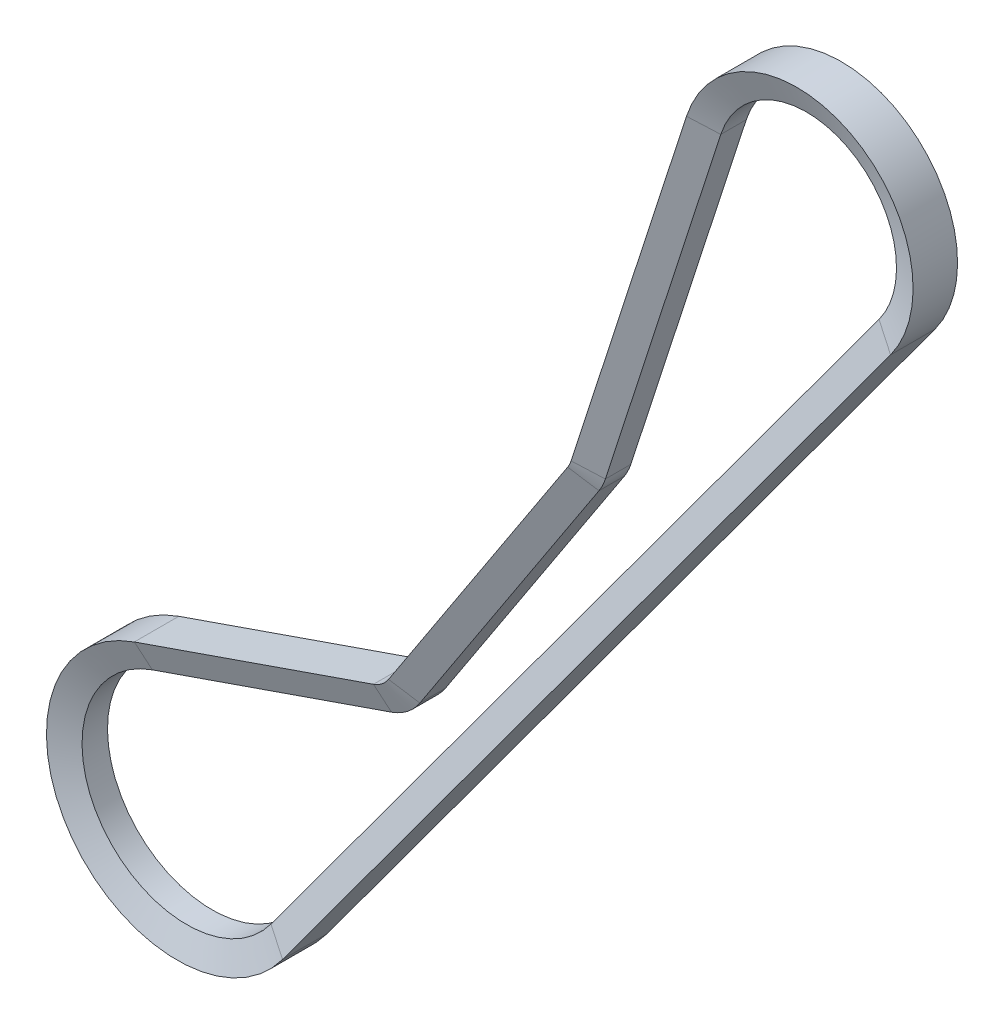
SolidWorks part; units mm, degrees
ref_plane "Front Plane" through (0, 0, 0) normal (0, 0, 1) x (1, 0, 0)
ref_plane "Top Plane" through (0, 0, 0) normal (0, 1, 0) x (1, 0, 0)
ref_plane "Right Plane" through (0, 0, 0) normal (1, 0, 0) x (0, 0, -1)
sketch "Sketch2" plane through (0, 0, 0) normal (0, 0, 1) x (1, 0, 0)
  line L0 (0, 0) -> (1, 0) construction
  line L1 (0, 0) -> (0, 1) construction
  line L12 (20.0468, -14.7273) -> (-110.1915, -192.0074)
  line L14 (-141.9298, -148.9752) -> (-90.7076, -131.214)
  line L15 (-87.4763, -128.6941) -> (-49.1172, -70.1401)
  line L16 (-48.3882, -68.6181) -> (-23.6632, 7.6693)
  arc A4 (-110.1915, -192.0074) -> (-141.9298, -148.9752) centre (-132.7567, -175.43) cw
  arc A7 (-23.6632, 7.6693) -> (20.0468, -14.7273) centre (0, 0) cw
  arc A8 (-90.7076, -131.214) -> (-87.4763, -128.6941) centre (-92.788, -125.2144) ccw
  arc A9 (-49.1172, -70.1401) -> (-48.3882, -68.6181) centre (-54.4289, -66.6603) ccw
ref_plane "Plane4" through (-23.6632, 7.6693, 0) normal (0.3083, 0.9513, 0) x (0.9513, -0.3083, 0)
sketch "Sketch3" plane through (-23.6632, 7.6693, 0) normal (0.3083, 0.9513, 0) x (0.9513, -0.3083, 0)
  line L0 (0, -4.7625) -> (0, 4.7625)
  line L1 (0, -4.7625) -> (5.588, -2.7286)
  line L2 (5.588, -2.7286) -> (5.588, 2.7286)
  line L3 (5.588, 2.7286) -> (0, 4.7625)
  line L4 (0, 0) -> (5.588, 0) construction
  dimension "D1" = 9.525
  dimension "D2" = 5.588
  dimension "D3" = 40
sweep "Sweep1" add profiles "Sketch3" path "Sketch2"
